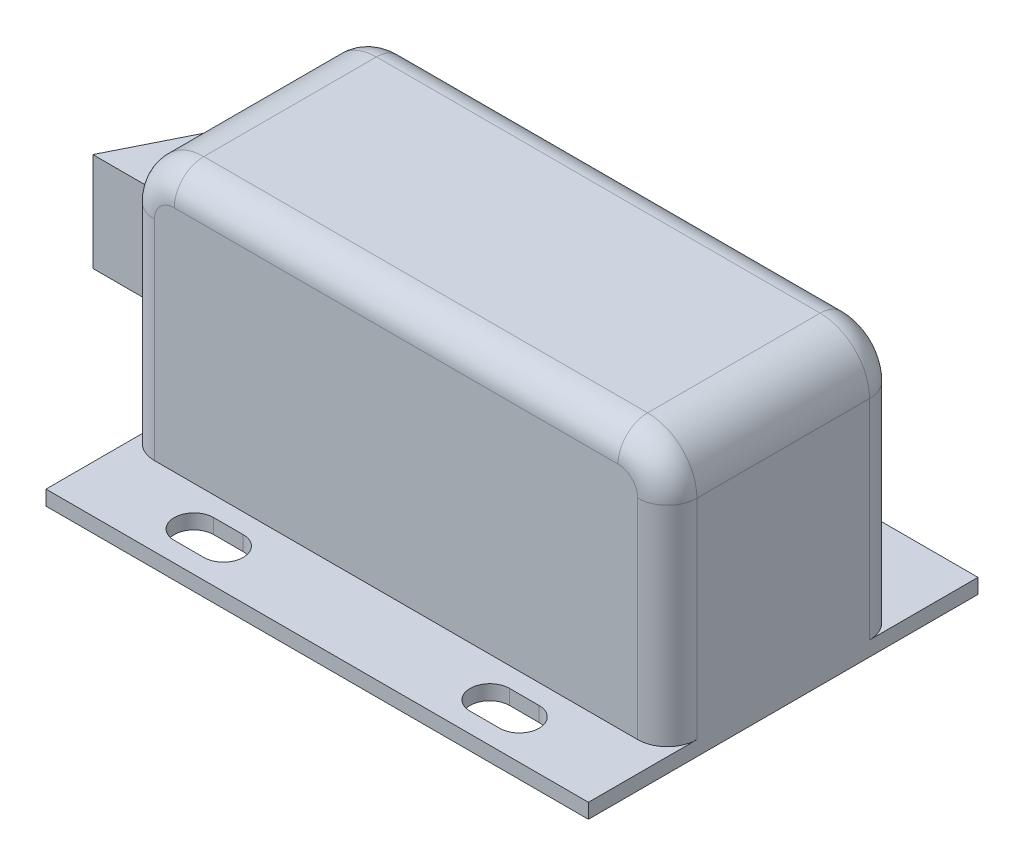
SolidWorks part; units mm, degrees
ref_plane "Front Plane" through (0, 0, 0) normal (0, 0, 1) x (1, 0, 0)
ref_plane "Top Plane" through (0, 0, 0) normal (0, 1, 0) x (1, 0, 0)
ref_plane "Right Plane" through (0, 0, 0) normal (1, 0, 0) x (0, 0, -1)
ref_plane "Plane1" through (0, 13.85, 0) normal (0, 1, 0) x (1, 0, 0)
sketch "Sketch1" plane through (0, 13.85, 0) normal (0, 1, 0) x (1, 0, 0)
  line L0 (-27.5, 8) -> (-27.5, -31.5)
  line L1 (-27.5, -31.5) -> (27.5, -31.5)
  line L2 (27.5, -31.5) -> (27.5, 8)
  line L3 (27.5, 8) -> (-27.5, 8)
extrude "Boss-Extrude1" add sketch "Sketch1" against normal blind 27.7
sketch "Sketch2" plane through (-27.5, 0, 0) normal (-1, 0, 0) x (0, 0, 1)
  line L0 (31.5, 13.85) -> (23.5, 13.85)
  line L1 (23.5, 13.85) -> (23.5, -12.35)
  line L2 (23.5, -12.35) -> (31.5, -12.35)
  line L3 (31.5, -12.35) -> (31.5, 13.85)
extrude "Cut-Extrude1" cut sketch "Sketch2" against normal through all
sketch "Sketch3" plane through (-27.5, 0, 0) normal (-1, 0, 0) x (0, 0, 1)
  line L0 (0, -12.35) -> (0, 13.85)
  line L1 (0, 13.85) -> (-8, 13.85)
  line L2 (-8, 13.85) -> (-8, -12.35)
  line L3 (-8, -12.35) -> (0, -12.35)
extrude "Cut-Extrude2" cut sketch "Sketch3" against normal through all
sketch "Sketch4" plane through (0, -12.35, 0) normal (0, 1, 0) x (-1, 0, 0)
  line L0 (-13.5, -2) -> (-16.5, -2)
  line L1 (-16.5, -6) -> (-13.5, -6)
  arc A0 (-16.5, -2) -> (-16.5, -6) centre (-16.5, -4) ccw
  arc A1 (-13.5, -6) -> (-13.5, -2) centre (-13.5, -4) ccw
extrude "Cut-Extrude3" cut sketch "Sketch4" against normal through all
sketch "Sketch5" plane through (0, -13.85, 0) normal (0, -1, 0) x (1, 0, 0)
  line L0 (-16.5, -6) -> (-13.5, -6)
  line L1 (-13.5, -2) -> (-16.5, -2)
  arc A0 (-13.5, -6) -> (-13.5, -2) centre (-13.5, -4) ccw
  arc A1 (-16.5, -2) -> (-16.5, -6) centre (-16.5, -4) ccw
extrude "Cut-Extrude4" cut sketch "Sketch5" against normal through all
sketch "Sketch6" plane through (0, -12.35, 0) normal (0, 1, 0) x (-1, 0, 0)
  line L0 (16.5, 29.5) -> (13.5, 29.5)
  line L1 (13.5, 25.5) -> (16.5, 25.5)
  arc A0 (13.5, 29.5) -> (13.5, 25.5) centre (13.5, 27.5) ccw
  arc A1 (16.5, 25.5) -> (16.5, 29.5) centre (16.5, 27.5) ccw
extrude "Cut-Extrude5" cut sketch "Sketch6" against normal through all
sketch "Sketch7" plane through (0, -13.85, 0) normal (0, -1, 0) x (1, 0, 0)
  line L0 (13.5, 25.5) -> (16.5, 25.5)
  line L1 (16.5, 29.5) -> (13.5, 29.5)
  arc A0 (16.5, 25.5) -> (16.5, 29.5) centre (16.5, 27.5) ccw
  arc A1 (13.5, 29.5) -> (13.5, 25.5) centre (13.5, 27.5) ccw
extrude "Cut-Extrude6" cut sketch "Sketch7" against normal through all
ref_plane "Plane2" through (0, -5.35, 0) normal (0, -1, 0) x (1, 0, 0)
sketch "Sketch8" plane through (0, -5.35, 0) normal (0, -1, 0) x (1, 0, 0)
  line L0 (-37.5, 16.75) -> (-32.5, 6.75)
  line L1 (-32.5, 6.75) -> (-27.5, 6.75)
  line L2 (-27.5, 6.75) -> (-27.5, 16.75)
  line L3 (-27.5, 16.75) -> (-37.5, 16.75)
extrude "Boss-Extrude2" add sketch "Sketch8" against normal blind 10
fillet "Fillet1" radius 5 2 edges at (27.5, 13.85, 11.75) (-27.5, 13.85, 11.75) tangent propagation no
fillet "Fillet2" radius 3 10 edges at (27.5, -1.75, 23.5) (26.0355, 12.3855, 23.5) (0, 13.85, 23.5) (-26.0355, 12.3855, 23.5) (-27.5, -1.75, 23.5) (-27.5, -1.75, 0) (-26.0355, 12.3855, 0) (0, 13.85, 0) (26.0355, 12.3855, 0) (27.5, -1.75, 0) tangent propagation no
